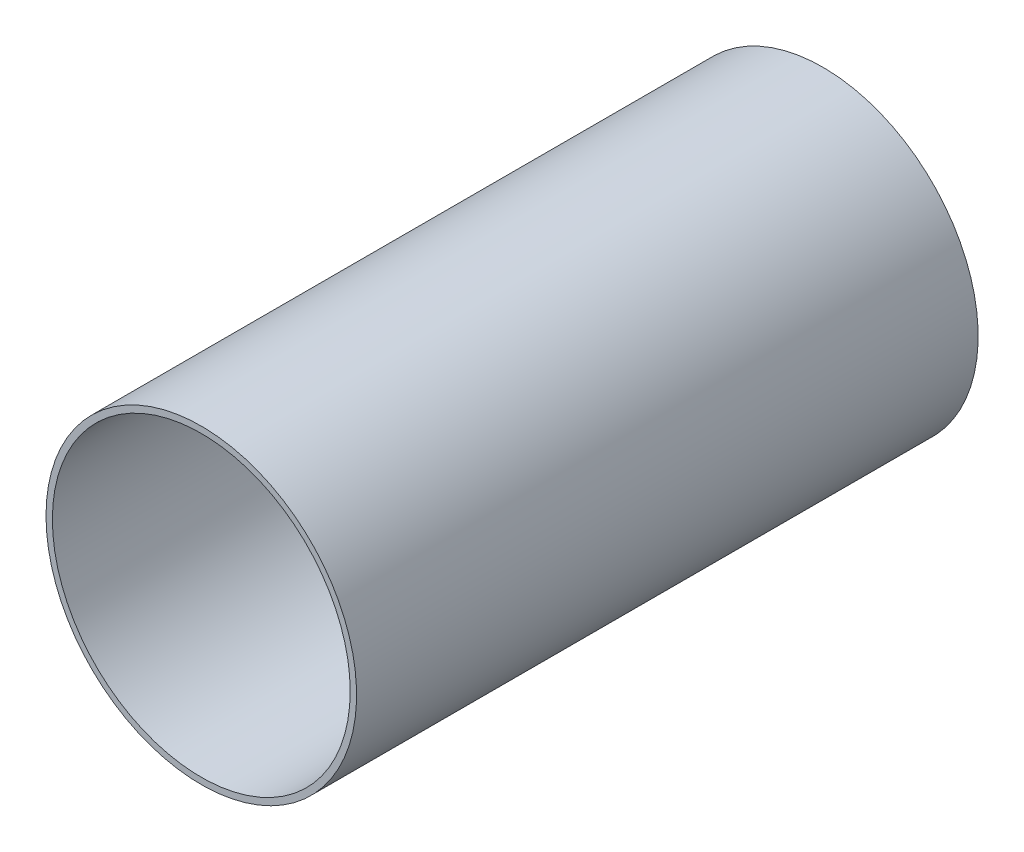
SolidWorks part; units mm, degrees
ref_plane "Front Plane" through (0, 0, 0) normal (0, 0, 1) x (1, 0, 0)
ref_plane "Top Plane" through (0, 0, 0) normal (0, 1, 0) x (1, 0, 0)
ref_plane "Right Plane" through (0, 0, 0) normal (1, 0, 0) x (0, 0, -1)
sketch "Sketch1" plane through (0, 0, 0) normal (0, 0, 1) x (1, 0, 0)
  circle A0 centre (0, 0) radius 38.0746
  circle A1 centre (0, 0) radius 36.5125
  dimension "D1" = 73.025
  dimension "D2" = 76.1492
extrude "Boss-Extrude1" add sketch "Sketch1" along normal mid plane 152.4
equation "\"AIRFRAME_OD\"= 3.091in"
equation "\"AIRFRAME_ID\"= 3.00in"
equation "\"FLAT_T\" = 0.125in"
equation "\"NOSE_EXP_L\"= 3.5in"
equation "\"NOSE_SHOULDER_L\" = 5in"
equation "\"MAIN_L\" = 30in"
equation "\"RECO_COUP_L\" = 6in"
equation "\"RECO_SWITCH_L\" = 1.5in"
equation "\"DROGUE_L\" = 14in"
equation "\"ATS_FORE_COUP_L\" = 4in"
equation "\"ATS_AFT_COUP_L\" = 4in"
equation "\"LOWER_L\" = 16in"
equation "\"FIN_N\" = 4"
equation "\"CR_AFT_X\" = 0.5in"
equation "\"CR_FORE_X\" = 6in"
equation "\"D1@Sketch1\"=\"COUPLER_ID\""
equation "\"D2@Sketch1\"=\"COUPLER_OD\""
equation "\"D1@Boss-Extrude1\"=\"RECO_COUP_L\""
equation "\"FIN_ROOT\" = 5in"
equation "\"FIN_X\" = 0.75in"
equation "\"MOTOR_OD\" = 2.25in"
equation "\"MOTOR_ID\" = 2.126in"
equation "\"COUPLER_OD\" = 2.998in"
equation "\"COUPLER_ID\" = 2.875in"
